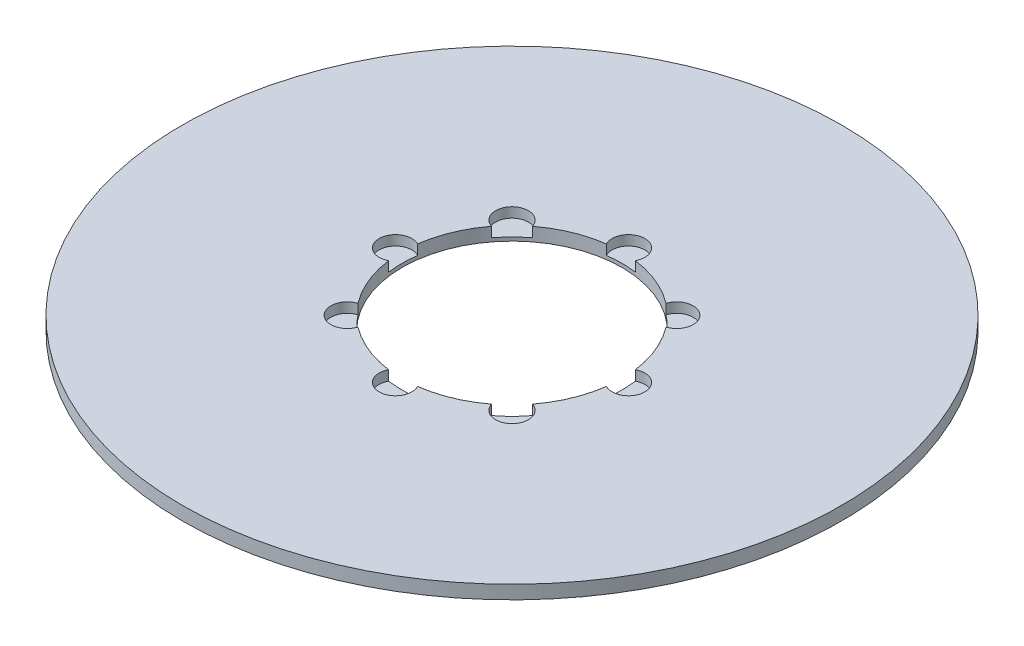
SolidWorks part; units mm, degrees
ref_plane "Front Plane" through (0, 0, 0) normal (0, 0, 1) x (1, 0, 0)
ref_plane "Top Plane" through (0, 0, 0) normal (0, 1, 0) x (1, 0, 0)
ref_plane "Right Plane" through (0, 0, 0) normal (1, 0, 0) x (0, 0, -1)
sketch "Sketch1" plane through (0, 0, 0) normal (0, 1, 0) x (1, 0, 0)
  circle A0 centre (0, 0) radius 97.5
  dimension "FLANGE_OD" = 195
extrude "Boss-Extrude1" add sketch "Sketch1" along normal blind 4
sketch "Sketch2" plane through (0, 0, 0) normal (0, 1, 0) x (1, 0, 0)
  circle A0 centre (0, 0) radius 32.5
  dimension "BORE_D" = 65
extrude "Cut-Extrude1" cut sketch "Sketch2" along normal through all
sketch "Sketch3" plane through (0, 4, 0) normal (0, 1, 0) x (1, 0, 0)
  circle A0 centre (0, 0) radius 34.4692 construction
  circle A1 centre (-34.4692, 0) radius 4.8352
  dimension "BOLT_D" = 9.6704
  dimension "BOLT_PCD" = 68.9384
extrude "Cut-Extrude2" cut sketch "Sketch3" against normal blind 2.9347
pattern_circular "CirPattern1" count 8 over 360 about axis through (0, 0, 0) along (0, 1, 0) of "Cut-Extrude2"
